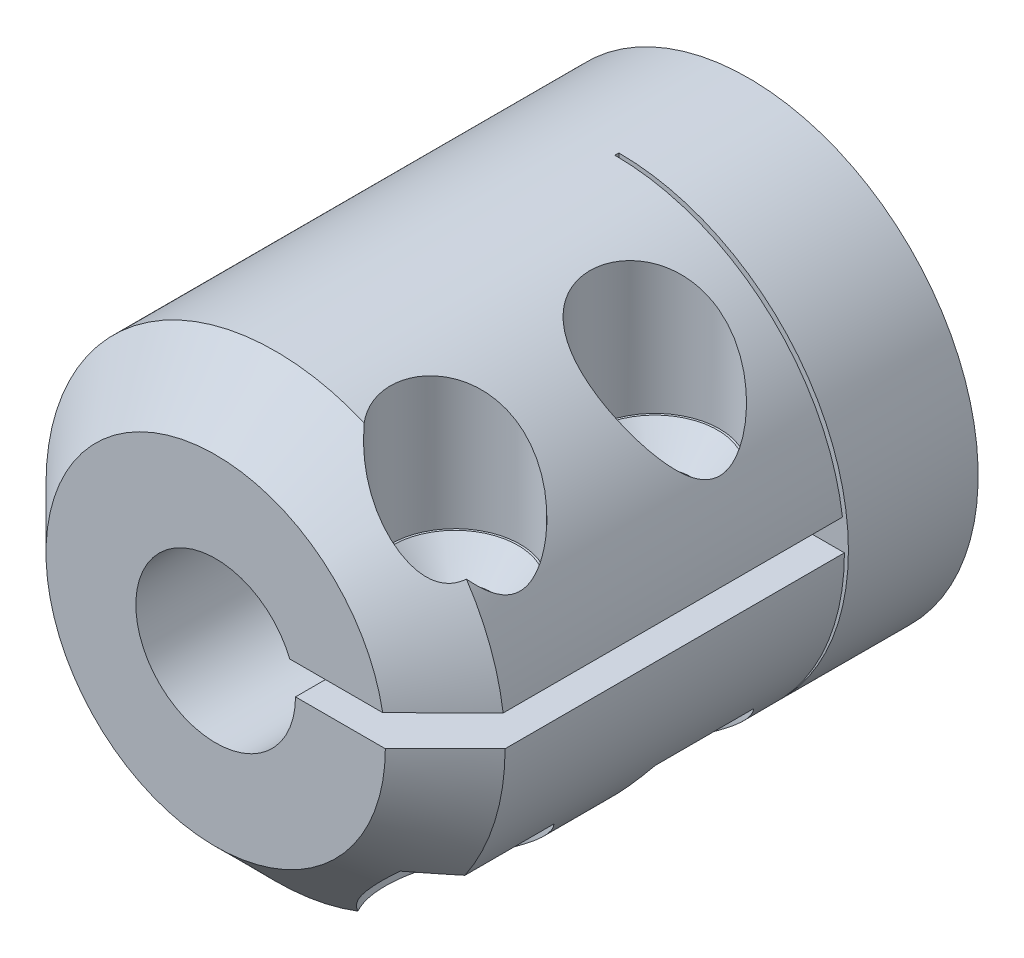
SolidWorks part; units mm, degrees
ref_plane "Płaszczyzna przednia" through (0, 0, 0) normal (0, 0, 1) x (1, 0, 0)
ref_plane "Płaszczyzna górna" through (0, 0, 0) normal (0, 1, 0) x (1, 0, 0)
ref_plane "Płaszczyzna prawa" through (0, 0, 0) normal (1, 0, 0) x (0, 0, -1)
sketch "Szkic1" plane through (0, 0, 0) normal (0, 0, 1) x (1, 0, 0)
  circle A0 centre (0, 0) radius 4
  circle A1 centre (0, 0) radius 11.5
  dimension "D1" = 8
  dimension "D2" = 23
extrude "Dodanie-wyciągnięcie1" add sketch "Szkic1" along normal blind 20
sketch "Szkic2" plane through (0, 0, 20) normal (0, 0, 1) x (1, 0, 0)
  line L0 (0, 0) -> (0, -1) construction
  line L1 (7, 4) -> (4, 4)
  line L2 (5.5, 4) -> (8.5, 4)
  line L3 (5.5, 4) -> (5.5, -6)
  line L4 (5.5, -6) -> (8.5, -6)
  line L5 (8.5, 4) -> (8.5, -6)
  line L6 (5.5, 4) -> (8.5, -6) construction
  line L7 (5.5, -6) -> (8.5, 4) construction
  line L8 (4, 4) -> (5.5, 1.5)
  line L9 (7, 4) -> (10, 4)
  line L10 (10, 4) -> (8.5, 1.5)
  line L11 (0, -1) -> (7, -1) construction
  line L12 (7, -1) -> (7, -5.1625) construction
  line L14 (4.9, -1) -> (9.1, -1)
  line L15 (4.9, -1) -> (4.9, -6)
  line L16 (4.9, -6) -> (9.1, -6)
  line L17 (9.1, -1) -> (9.1, -6)
  line L18 (4.9, -1) -> (9.1, -6) construction
  line L19 (4.9, -6) -> (9.1, -1) construction
  point P3 (7, -1)
  point P13 (7, -3.5)
  point P20 (9.1, -1.7018)
  point P21 (9.1, -1.1901)
  point P22 (0, 0)
  dimension "D1" = 10
  dimension "D2" = 3
  dimension "D3" = 6
  dimension "D4" = 2.5
  dimension "D5" = 1
  dimension "D6" = 7
  dimension "D7" = 4.2
  dimension "D8" = 5
sketch "Szkic3" plane through (0, 0, 0) normal (0, 1, 0) x (1, 0, 0)
  line L1 (0, 0) -> (11.5, 0)
  line L2 (0, 0) -> (0, -20)
  line L3 (0, -20) -> (11.5, -20)
  line L4 (11.5, 0) -> (11.5, -20)
extrude "Wytnij-wyciągnięcie1" cut sketch "Szkic3" along normal blind 1.5
ref_plane "Płaszczyzna1" through (0, 4, 0) normal (0, 1, 0) x (1, 0, 0)
sketch "Szkic4" plane through (0, 4, 0) normal (0, 1, 0) x (1, 0, 0)
  line L0 (7, -20) -> (7, 0)
  line L1 (11.4018, 0) -> (3.7081, 0) construction
  line L2 (7, -10) -> (7, -20) construction
  line L3 (7, -10) -> (-15.8022, -10) construction
  circle A0 centre (7, -15) radius 3.25
  circle A1 centre (7, -5) radius 3.25
  dimension "D1" = 6.5
  dimension "D2" = 10
extrude "Wytnij-wyciągnięcie2" cut sketch "Szkic4" along normal blind 32 contours L0 A0 | A1 L0 | A1 L0 | L0 A0 region at (5.6207, 4, 15) region at (5.6207, 4, 5) region at (8.3793, 4, 5) region at (8.3793, 4, 15)
hole_wizard "Pogłębienie stożkowe pod M3 Wkręt z łbem płaskim1" positions "Szkic 3D1" profile "Szkic5" countersink size "M3" standard "DIN" end condition through all
sketch3d "Szkic 3D1"
  line L0 (7, 8.4547, 15) -> (7, 4, 15) construction
  line L1 (7, 8.4627, 5) -> (7, 4, 5) construction
  point P0 (7, 4, 15)
  point P4 (7, 4, 5)
sketch "Szkic5" plane through (7, 4, 15) normal (1, 0, 0) x (0, 0, 1)
  line L0 (0, 0) -> (0, 15.5)
  line L1 (0, 15.5) -> (1.8, 15.5)
  line L2 (1.8, 15.5) -> (1.8, 1.35)
  line L3 (1.8, 1.35) -> (3.15, 0)
  line L5 (3.15, 0) -> (0, 0)
  line L6 (-1.8, 1.35) -> (-3.15, 0) construction
  line L11 (0, -6.35) -> (0, 107.95) construction
  dimension "Średnica otworu na wylot" = 3.6
  dimension "Głębokość otworu na wylot" = 15.5
  dimension "Średnica zewnętrznego pogłębienia stożkowego" = 6.3
  dimension "Kąt zewnętrznego pogłębienia stożkowego" = 90
ref_plane "Płaszczyzna2" through (0, -6.5, 0) normal (0, -1, 0) x (-1, 0, 0)
sketch "Szkic7" plane through (0, -6.5, 0) normal (0, -1, 0) x (-1, 0, 0)
  line L0 (-11.5, -10) -> (11.5, -10) construction
  line L1 (-11.5, -20) -> (-11.5, 0) construction
  line L2 (11.5, -20) -> (11.5, 0) construction
  circle A0 centre (-7, -5) radius 3.5
  circle A1 centre (-7, -15) radius 3.5
  dimension "D1" = 7
extrude "Wytnij-wyciągnięcie3" cut sketch "Szkic7" along normal blind 32
sketch "Szkic8" plane through (0, -6.5, 0) normal (0, -1, 0) x (1, 0, 0)
  line L0 (11.5, 10) -> (-11.5, 10) construction
  line L1 (11.5, 20) -> (11.5, 0) construction
  line L2 (-11.5, 20) -> (-11.5, 0) construction
  circle A0 centre (7, 15) radius 2
  circle A1 centre (7, 5) radius 2
  dimension "D1" = 4
extrude "Wytnij-wyciągnięcie4" cut sketch "Szkic8" against normal blind 7 contours A0 | A1
sketch "Szkic9" plane through (0, 0, 0) normal (0, 0, -1) x (-1, 0, 0)
  line L0 (0, 0) -> (0, 12.2687)
  line L1 (0, 0) -> (0, -12.6536)
  line L4 (-11.4018, 1.5) -> (-3.7081, 1.5)
  line L5 (-4, 0) -> (-11.5, 0)
  line L6 (-11.4018, 1.5) -> (-3.7081, 1.5)
  line L7 (-4, 0) -> (-11.5, 0)
  arc A2 (-11.5, 0) -> (-11.4018, 1.5) centre (0, 0) ccw
  arc A3 (-4, 0) -> (-3.7081, 1.5) centre (0, 0) ccw
  arc A4 (-11.5, 0) -> (-11.4018, 1.5) centre (0, 0) ccw
  arc A5 (-4, 0) -> (-3.7081, 1.5) centre (0, 0) ccw
  arc M5 (-11.5, 0) -> (-11.4018, 1.5) centre (0, 0) ccw
  arc M7 (-3.7081, 1.5) -> (-4, 0) centre (0, 0) cw
  dimension "D1" = 0
extrude "Dodanie-wyciągnięcie2" add sketch "Szkic9" along normal blind 0.2 contours L1 L0 M7 M5 region at (-5.3189, 0, 0)
sketch "Szkic10" plane through (0, 0, -0.2) normal (0, 0, -1) x (-1, 0, 0)
  circle A0 centre (0, 0) radius 11.5
extrude "Dodanie-wyciągnięcie3" add sketch "Szkic10" along normal blind 1.5
sketch "Szkic11" plane through (0, 0, -1.7) normal (0, 0, -1) x (-1, 0, 0)
  line L1 (-5, 5) -> (5, 5)
  line L2 (-5, 5) -> (-5, -5)
  line L3 (-5, -5) -> (5, -5)
  line L4 (5, 5) -> (5, -5)
  line L5 (-5, 5) -> (5, -5) construction
  line L6 (-5, -5) -> (5, 5) construction
  circle A0 centre (0, 0) radius 11.5
  dimension "D1" = 10
extrude "Dodanie-wyciągnięcie4" add sketch "Szkic11" along normal blind 5
chamfer "Sfazowanie1" distance 3 angle 45 1 edges at (-11.4754, -0.7516, 20)
